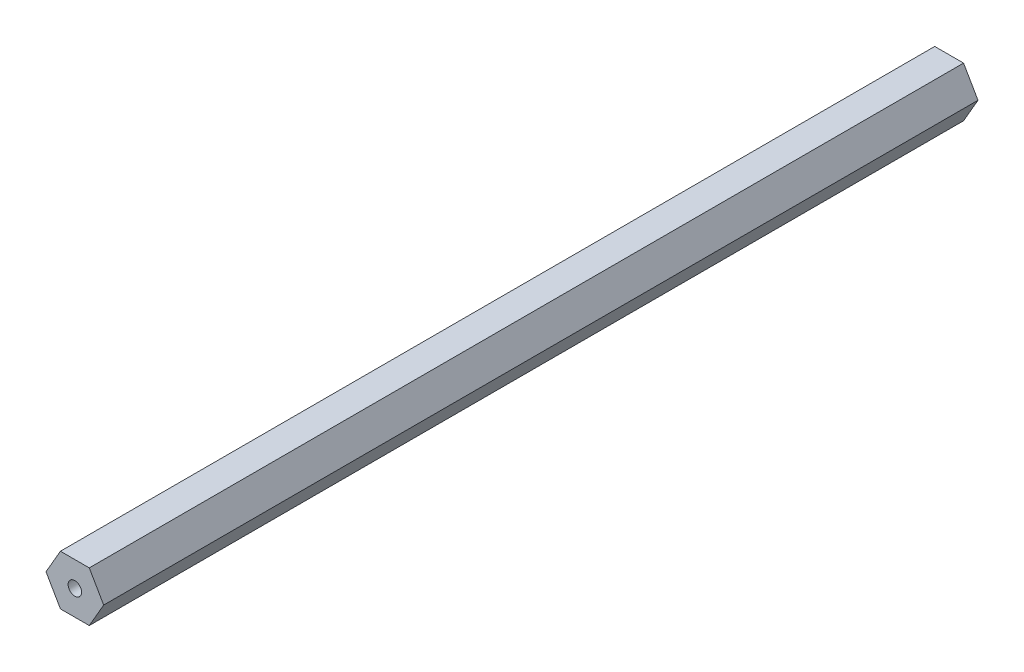
SolidWorks part; units mm, degrees
material "7075-T6 (SN)"
ref_plane "Front Plane" through (0, 0, 0) normal (0, 0, 1) x (1, 0, 0)
ref_plane "Top Plane" through (0, 0, 0) normal (0, 1, 0) x (1, 0, 0)
ref_plane "Right Plane" through (0, 0, 0) normal (1, 0, 0) x (0, 0, -1)
other "Configuration Table"
sketch "Sketch1" plane through (0, 0, 0) normal (0, 0, 1) x (1, 0, 0)
  line L1 (7.3323, 0) -> (3.6662, 6.35)
  line L2 (3.6662, 6.35) -> (-3.6662, 6.35)
  line L3 (-3.6662, 6.35) -> (-7.3323, 0)
  line L4 (-7.3323, 0) -> (-3.6662, -6.35)
  line L5 (-3.6662, -6.35) -> (3.6662, -6.35)
  line L6 (3.6662, -6.35) -> (7.3323, 0)
  circle A0 centre (0, 0) radius 6.35 construction
  circle A1 centre (0, 0) radius 1.7145
  dimension "D2" = 3.429
  dimension "D1" = 12.7
extrude "Boss-Extrude1" add sketch "Sketch1" along normal blind 222.25
equation "\"length\" = 8.75"
equation "\"D1@Boss-Extrude1\"=\"length\""
